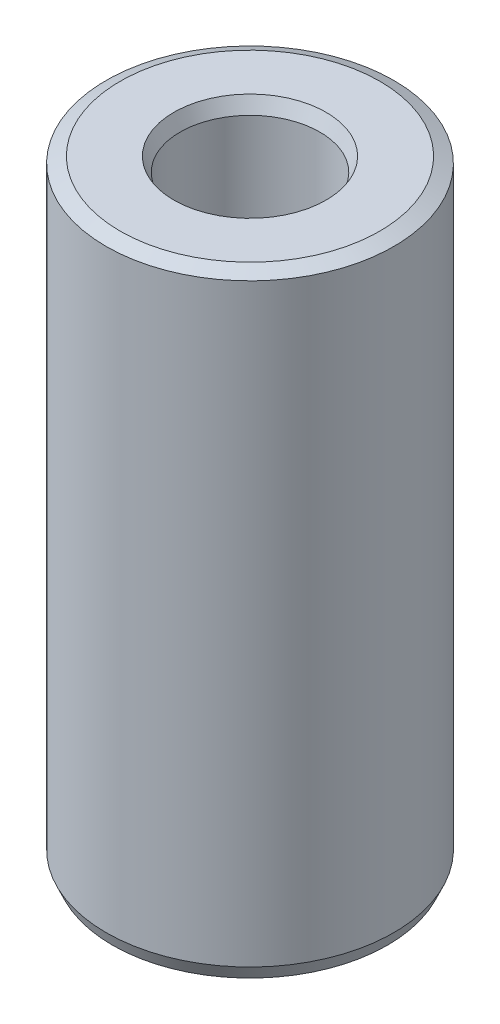
SolidWorks part; units mm, degrees
ref_plane "Front Plane" through (0, 0, 0) normal (0, 0, 1) x (1, 0, 0)
ref_plane "Top Plane" through (0, 0, 0) normal (0, 1, 0) x (1, 0, 0)
ref_plane "Right Plane" through (0, 0, 0) normal (1, 0, 0) x (0, 0, -1)
sketch "Sketch1" plane through (0, 0, 0) normal (0, 1, 0) x (1, 0, 0)
  circle A0 centre (0, 0) radius 32.5
  dimension "SLEEVE_OD" = 65
extrude "Boss-Extrude1" add sketch "Sketch1" along normal blind 138.8417
sketch "Sketch2" plane through (0, 0, 0) normal (0, 1, 0) x (1, 0, 0)
  circle A0 centre (0, 0) radius 15.7864
  dimension "BORE_D" = 31.5728
extrude "Cut-Extrude1" cut sketch "Sketch2" along normal through all
chamfer "Chamfer1" distance 1.4155 angle 65.895 4 edges at (0, 138.8417, 15.7864) (0, 0, 15.7864) (0, 0, 32.5) (0, 138.8417, 32.5) first distance on face at (0, 138.8417, 15.7864) first distance on face at (0, 0, 15.7864) first distance on face at (0, 138.8417, 32.5)
